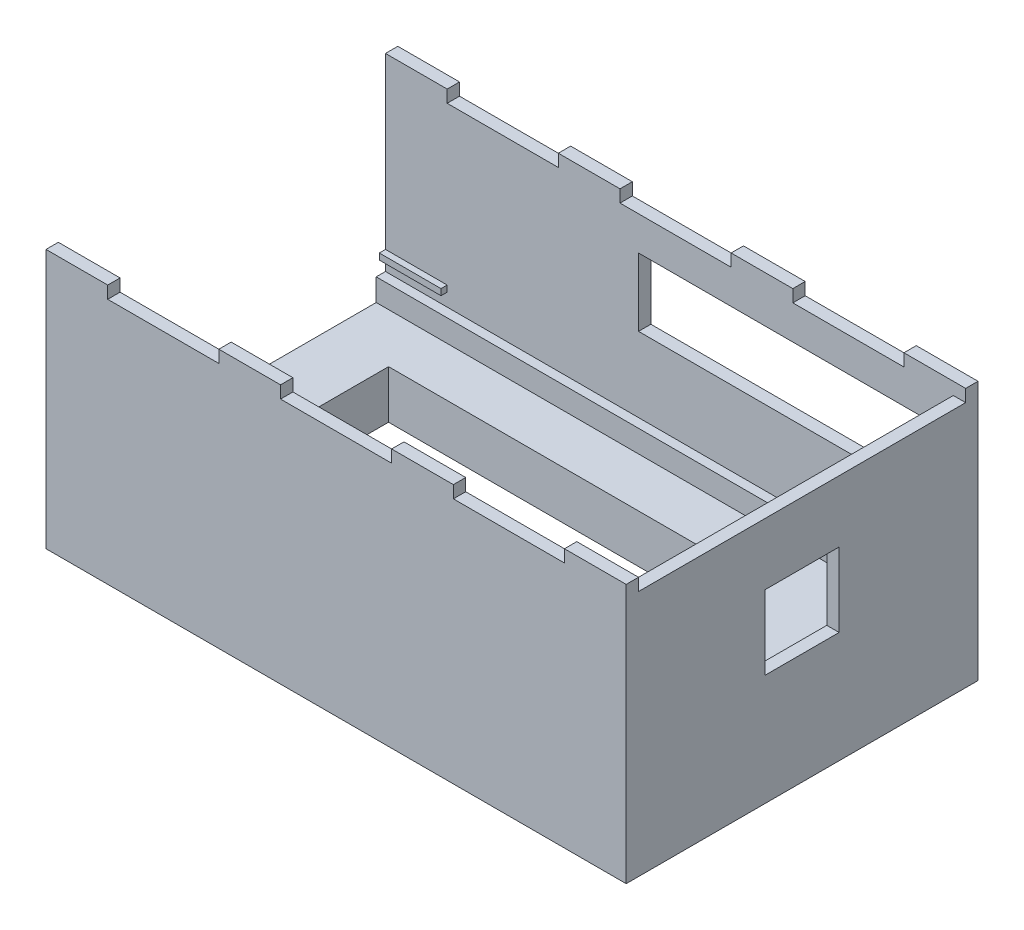
SolidWorks part; units mm, degrees
ref_plane "Front Plane" through (0, 0, 0) normal (0, 0, 1) x (1, 0, 0)
ref_plane "Top Plane" through (0, 0, 0) normal (0, 1, 0) x (1, 0, 0)
ref_plane "Right Plane" through (0, 0, 0) normal (1, 0, 0) x (0, 0, -1)
sketch "Sketch1" plane through (0, 0, 0) normal (0, 1, 0) x (1, 0, 0)
  line L1 (-30.298, 32.6459) -> (63.702, 32.6459)
  line L2 (-30.298, 32.6459) -> (-30.298, -24.3541)
  line L3 (-30.298, -24.3541) -> (63.702, -24.3541)
  line L4 (63.702, 32.6459) -> (63.702, -24.3541)
  dimension "D1" = 94
  dimension "D2" = 57
extrude "Boss-Extrude1" add sketch "Sketch1" along normal blind 10
sketch "Sketch2" plane through (0, 10, 0) normal (0, 1, 0) x (1, 0, 0)
  line L0 (-30.298, 32.6459) -> (63.702, 32.6459)
  line L1 (63.702, 32.6459) -> (63.702, -24.3541)
  line L2 (63.702, -24.3541) -> (-30.298, -24.3541)
  line L3 (-30.298, -24.3541) -> (-30.298, -22.3541)
  line L4 (-30.298, 32.6459) -> (-30.298, -24.3541) construction
  line L5 (-30.298, -22.3541) -> (61.702, -22.3541)
  line L6 (61.702, -22.3541) -> (61.702, 30.6459)
  line L7 (61.702, 30.6459) -> (-30.298, 30.6459)
  line L8 (-30.298, 30.6459) -> (-30.298, 32.6459)
  dimension "D1" = 2
  dimension "D2" = 2
  dimension "D3" = 2
extrude "Boss-Extrude2" add sketch "Sketch2" along normal blind 30
sketch "Sketch3" plane through (-30.298, 0, 0) normal (-1, 0, 0) x (0, 0, 1)
  line L0 (-30.6459, 40) -> (-30.6459, 10) construction
  line L1 (-30.6459, 10) -> (-29.1459, 10)
  line L2 (-30.6459, 10) -> (-30.6459, 11.4)
  line L3 (-30.6459, 11.4) -> (-29.1459, 11.4)
  line L4 (-29.1459, 10) -> (-29.1459, 11.4)
  line L5 (22.3541, 10) -> (20.8541, 10)
  line L6 (22.3541, 10) -> (22.3541, 11.4)
  line L7 (22.3541, 11.4) -> (20.8541, 11.4)
  line L8 (20.8541, 10) -> (20.8541, 11.4)
  line L9 (-30.6459, 14.5) -> (-29.6459, 14.5)
  line L10 (-30.6459, 14.5) -> (-30.6459, 13.5)
  line L11 (-30.6459, 13.5) -> (-29.6459, 13.5)
  line L12 (-29.6459, 14.5) -> (-29.6459, 13.5)
  line L13 (22.3541, 40) -> (22.3541, 10) construction
  line L14 (22.3541, 13.5) -> (21.3541, 13.5)
  line L15 (22.3541, 13.5) -> (22.3541, 14.5)
  line L16 (22.3541, 14.5) -> (21.3541, 14.5)
  line L17 (21.3541, 13.5) -> (21.3541, 14.5)
  dimension "D1" = 1.5
  dimension "D2" = 1.4
  dimension "D3" = 1.5
  dimension "D4" = 1.4
  dimension "D5" = 2.1
  dimension "D6" = 2.1
  dimension "D8" = 1
  dimension "D9" = 1
  dimension "D10" = 1
  dimension "D11" = 1
extrude "Boss-Extrude3" add sketch "Sketch3" against normal up to surface (92 mm away) contours L1 L4 L3 L2 | L5 L8 L7 L6 | L17 L16 L15 L14 up to face at (61.702, 25, -4.1459)
extrude "Boss-Extrude4" add sketch "Sketch3<3>" against normal blind 10 contours L12 L11 L10 L9
sketch "Sketch3<3>" plane through (-30.298, 0, 0) normal (-1, 0, 0) x (0, 0, 1) same geometry as "Sketch3"
sketch "Sketch4" plane through (0, 0, -32.6459) normal (0, 0, -1) x (-1, 0, 0)
  line L0 (-63.702, 40) -> (-63.702, 0) construction
  line L1 (-56.702, 34.5) -> (-10.702, 34.5)
  line L2 (-56.702, 34.5) -> (-56.702, 23.5)
  line L3 (-56.702, 23.5) -> (-10.702, 23.5)
  line L4 (-10.702, 34.5) -> (-10.702, 23.5)
  point P4 (-56.702, 29)
  dimension "D1" = 7
  dimension "D2" = 46
  dimension "D3" = 11
  dimension "D4" = 9
extrude "Cut-Extrude1" cut sketch "Sketch4" against normal blind 10
sketch "Sketch5" plane through (63.702, 0, 0) normal (1, 0, 0) x (0, 0, -1)
  line L1 (-1.8541, 30) -> (10.1459, 30)
  line L2 (-1.8541, 30) -> (-1.8541, 18)
  line L3 (-1.8541, 18) -> (10.1459, 18)
  line L4 (10.1459, 30) -> (10.1459, 18)
  line L5 (-24.3541, 40) -> (32.6459, 40) construction
  line L6 (4.1459, 40) -> (4.1459, 0) construction
  line L8 (-24.3541, 0) -> (32.6459, 0) construction
  point P10 (4.1459, 30)
  dimension "D1" = 0
  dimension "D2" = 12
  dimension "D3" = 10
  dimension "D4" = 12
extrude "Cut-Extrude2" cut sketch "Sketch5" against normal up to surface (2 mm away) up to face at (61.702, 16.8, 4.5207)
ref_plane "Plane5" through (0, 33, 0) normal (0, 1, 0) x (1, 0, 0)
sketch "Sketch7" plane through (0, 33, 0) normal (0, 1, 0) x (1, 0, 0)
  line L0 (61.702, -22.3541) -> (-30.298, -22.3541) construction
  line L1 (10.702, -22.3541) -> (61.702, -22.3541)
  line L2 (10.702, -22.3541) -> (10.702, -20.3541)
  line L3 (10.702, -20.3541) -> (59.702, -20.3541)
  line L4 (61.702, -22.3541) -> (61.702, -20.3541)
  line L5 (61.702, 29.1459) -> (61.702, -20.8541) construction
  line L6 (61.702, 30.6459) -> (61.702, -22.3541) construction
  line L8 (59.702, -20.3541) -> (59.702, 15.6459)
  line L9 (59.702, 15.6459) -> (61.702, 15.6459)
  line L10 (61.702, -20.3541) -> (61.702, 15.6459)
  dimension "D1" = 51
  dimension "D2" = 2
  dimension "D3" = 38
  dimension "D4" = 2
extrude "Boss-Extrude5" add sketch "Sketch7" against normal blind 2 contours L3 L8 L9 L10 L4 L1 L2
fillet "Fillet1" radius 1.5 2 edges at (59.702, 31, 2.3541) (35.202, 31, 20.3541) conic radius 3
ref_plane "Plane6" through (0, 34.8, 0) normal (0, 1, 0) x (1, 0, 0)
sketch "Sketch8" plane through (0, 34.8, 0) normal (0, 1, 0) x (1, 0, 0)
  line L1 (10.702, -20.3541) -> (59.702, -20.3541)
  line L2 (10.702, -20.3541) -> (10.702, -22.3541)
  line L3 (10.702, -22.3541) -> (61.702, -22.3541)
  line L4 (61.702, -20.3541) -> (61.702, -22.3541)
  line L5 (61.702, -22.3541) -> (59.702, -22.3541)
  line L6 (61.702, -22.3541) -> (61.702, 15.6459)
  line L7 (61.702, 15.6459) -> (59.702, 15.6459)
  line L8 (59.702, -20.3541) -> (59.702, 15.6459)
extrude "Boss-Extrude6" add sketch "Sketch8" along normal blind 1 contours L6 L7 L8 L1 L2 L3
sketch "Sketch9" plane through (0, 40, 0) normal (0, 1, 0) x (1, 0, 0)
  line L0 (-30.298, 30.6459) -> (61.702, 30.6459) construction
  line L1 (-30.298, 32.6459) -> (-20.298, 32.6459)
  line L2 (-30.298, 32.6459) -> (-30.298, 30.6459)
  line L3 (-30.298, 30.6459) -> (-20.298, 30.6459)
  line L4 (-20.298, 32.6459) -> (-20.298, 30.6459)
  line L5 (61.702, 30.6459) -> (-30.298, 30.6459) construction
  line L6 (-2.298, 30.6459) -> (7.702, 30.6459)
  line L7 (-2.298, 30.6459) -> (-2.298, 32.6459)
  line L8 (-2.298, 32.6459) -> (7.702, 32.6459)
  line L9 (7.702, 30.6459) -> (7.702, 32.6459)
  line L10 (63.702, 32.6459) -> (-30.298, 32.6459) construction
  line L11 (61.702, -22.3541) -> (-30.298, -22.3541) construction
  line L12 (25.702, 30.6459) -> (35.702, 30.6459)
  line L13 (25.702, 30.6459) -> (25.702, 32.6459)
  line L14 (25.702, 32.6459) -> (35.702, 32.6459)
  line L15 (35.702, 30.6459) -> (35.702, 32.6459)
  line L16 (53.702, 30.6459) -> (63.702, 30.6459)
  line L17 (53.702, 30.6459) -> (53.702, 32.6459)
  line L18 (53.702, 32.6459) -> (63.702, 32.6459)
  line L19 (63.702, 30.6459) -> (63.702, 32.6459)
  line L20 (-30.298, -24.3541) -> (-20.298, -24.3541)
  line L21 (-30.298, -24.3541) -> (-30.298, -22.3541)
  line L22 (-30.298, -22.3541) -> (-20.298, -22.3541)
  line L23 (-20.298, -24.3541) -> (-20.298, -22.3541)
  line L24 (-30.298, -24.3541) -> (63.702, -24.3541) construction
  line L25 (-2.298, -24.3541) -> (7.702, -24.3541)
  line L26 (-2.298, -24.3541) -> (-2.298, -22.3541)
  line L27 (-2.298, -22.3541) -> (7.702, -22.3541)
  line L28 (7.702, -24.3541) -> (7.702, -22.3541)
  line L29 (10.702, -22.3541) -> (61.702, -22.3541) construction
  line L30 (25.702, -24.3541) -> (35.702, -24.3541)
  line L31 (25.702, -24.3541) -> (25.702, -22.3541)
  line L32 (25.702, -22.3541) -> (35.702, -22.3541)
  line L33 (35.702, -24.3541) -> (35.702, -22.3541)
  line L35 (63.702, -24.3541) -> (53.702, -24.3541)
  line L36 (63.702, -24.3541) -> (63.702, -22.3541)
  line L37 (63.702, -22.3541) -> (53.702, -22.3541)
  line L38 (53.702, -24.3541) -> (53.702, -22.3541)
  dimension "D1" = 10
  dimension "D2" = 10
  dimension "D3" = 18
  dimension "D4" = 18
  dimension "D5" = 10
  dimension "D6" = 18
  dimension "D7" = 18
  dimension "D8" = 18
  dimension "D9" = 18
  dimension "D10" = 10
  dimension "D11" = 10
  dimension "D12" = 10
extrude "Boss-Extrude7" add sketch "Sketch9" along normal blind 2
sketch "Sketch10" plane through (0, 10, 0) normal (0, 1, 0) x (1, 0, 0)
  line L0 (-30.298, 4.1459) -> (61.702, 4.1459) construction
  line L1 (-20.298, 21.1459) -> (31.702, 21.1459)
  line L2 (-20.298, 21.1459) -> (-20.298, -12.8541)
  line L3 (-20.298, -12.8541) -> (31.702, -12.8541)
  line L4 (31.702, 21.1459) -> (31.702, -12.8541)
  line L5 (-30.298, 29.1459) -> (-30.298, -20.8541) construction
  line L6 (61.702, 30.6459) -> (61.702, -22.3541) construction
  point P10 (31.702, 4.1459)
  dimension "D1" = 34
  dimension "D2" = 0
  dimension "D3" = 52
  dimension "D4" = 10
extrude "Cut-Extrude3" cut sketch "Sketch10" against normal through all and the other way through all
sketch "Sketch11" plane through (0, 10, 0) normal (0, 1, 0) x (1, 0, 0)
  line L1 (61.702, 29.1459) -> (-30.298, 29.1459)
  line L2 (61.702, 29.1459) -> (61.702, -20.8541)
  line L3 (61.702, -20.8541) -> (-30.298, -20.8541)
  line L4 (-30.298, 29.1459) -> (-30.298, -20.8541)
extrude "Cut-Extrude4" cut sketch "Sketch11" against normal blind 2.2
